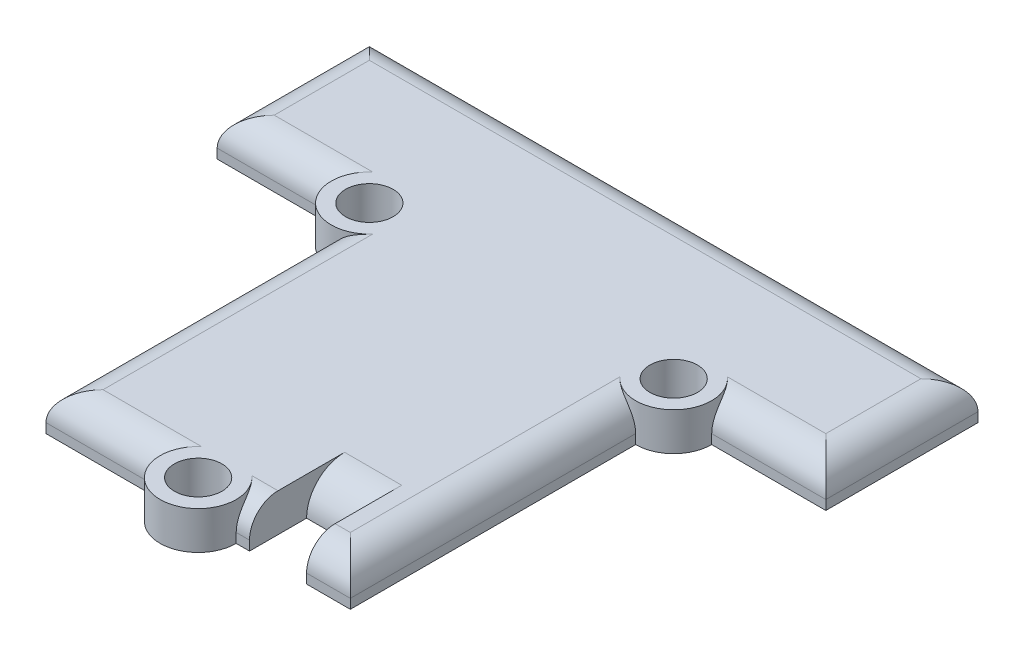
SolidWorks part; units mm, degrees
ref_plane "Plan de face" through (0, 0, 0) normal (0, 0, 1) x (1, 0, 0)
ref_plane "Plan de dessus" through (0, 0, 0) normal (0, 1, 0) x (1, 0, 0)
ref_plane "Plan de droite" through (0, 0, 0) normal (1, 0, 0) x (0, 0, -1)
sketch "Esquisse1" plane through (0, 0, 0) normal (0, 1, 0) x (1, 0, 0)
  line L1 (0, 0) -> (32, 0)
  line L2 (0, 0) -> (0, 8)
  line L3 (0, 8) -> (32, 8)
  line L4 (32, 0) -> (32, 8)
  dimension "D1" = 32
  dimension "D2" = 8
extrude "Boss.-Extru.1" add sketch "Esquisse1" along normal blind 2
sketch "Esquisse2" plane through (0, 2, 0) normal (0, 1, 0) x (1, 0, 0)
  line L0 (0, 0) -> (32, 0) construction
  line L1 (8, 0) -> (24, 0)
  line L2 (8, 0) -> (8, -17)
  line L3 (8, -17) -> (24, -17)
  line L4 (24, 0) -> (24, -17)
  point P6 (16, -17)
  point P7 (16, 0)
  dimension "D1" = 0
  dimension "D2" = 16
  dimension "D3" = 17
extrude "Boss.-Extru.2" add sketch "Esquisse2" against normal blind 2
sketch "Esquisse3" plane through (0, 2, 0) normal (0, 1, 0) x (1, 0, 0)
  line L0 (8, -17) -> (24, -17) construction
  circle A0 centre (8, 0) radius 2
  circle A1 centre (24, 0) radius 2
  circle A2 centre (16, -17) radius 2
  dimension "D1" = 4
  dimension "D2" = 4
  dimension "D3" = 4
extrude "Boss.-Extru.3" add sketch "Esquisse3" against normal blind 2
sketch "Esquisse4" plane through (0, 2, 0) normal (0, 1, 0) x (1, 0, 0)
  circle A0 centre (8, 0) radius 1.25
  circle A1 centre (24, 0) radius 1.25
  circle A2 centre (16, -17) radius 1.25
  dimension "D1" = 2.5
  dimension "D2" = 2.5
  dimension "D3" = 2.5
extrude "Enlèv. mat.-Extru.1" cut sketch "Esquisse4" against normal blind 2
fillet "Congé1" radius 1.5 9 edges at (21, 2, 17) (11, 2, 17) (29, 2, 0) (3, 2, 0) (24, 2, 9.5) (8, 2, 9.5) (32, 2, -4) (0, 2, -4) (16, 2, -8)
sketch "Esquisse5" plane through (0, 0, 0) normal (0, -1, 0) x (1, 0, 0)
  line L0 (18, 17) -> (24, 17) construction
  line L1 (21.7, 17) -> (18.7, 17)
  line L2 (21.7, 17) -> (21.7, 14)
  line L3 (21.7, 14) -> (18.7, 14)
  line L4 (18.7, 17) -> (18.7, 14)
  arc A0 (18, 17) -> (14, 17) centre (16, 17) ccw construction
  point P6 (20.2, 17)
  point P10 (16, 19)
  dimension "D1" = 3
  dimension "D2" = 4.2
  dimension "D3" = 3
extrude "Enlèv. mat.-Extru.2" cut sketch "Esquisse5" against normal through all
fillet "Congé2" radius 2 1 edges at (20.2, 2, 14)
